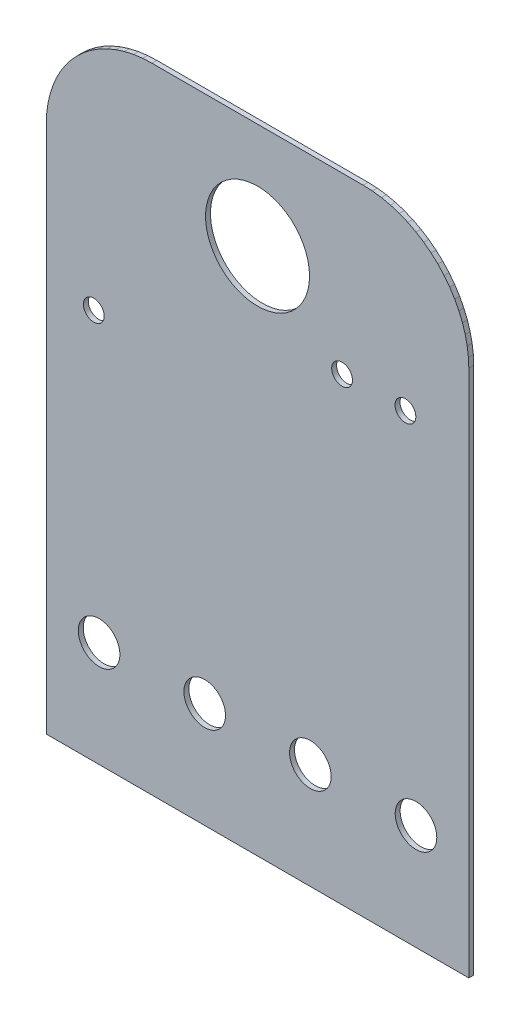
SolidWorks part; units mm, degrees
ref_plane "Front Plane" through (0, 0, 0) normal (0, 0, 1) x (1, 0, 0)
ref_plane "Top Plane" through (0, 0, 0) normal (0, 1, 0) x (1, 0, 0)
ref_plane "Right Plane" through (0, 0, 0) normal (1, 0, 0) x (0, 0, -1)
sketch "Model" plane through (0, 0, 0) normal (0, 0, 1) x (1, 0, 0)
  line L0 (0, 0) -> (258.064, 0)
  line L1 (258.064, 0) -> (258.064, 322.58)
  line L2 (258.064, 322.58) -> (257.8185, 328.2029)
  line L3 (257.8185, 328.2029) -> (257.0839, 333.7831)
  line L4 (257.0839, 333.7831) -> (255.8657, 339.278)
  line L5 (255.8657, 339.278) -> (254.1732, 344.6458)
  line L6 (254.1732, 344.6458) -> (252.0194, 349.8456)
  line L7 (252.0194, 349.8456) -> (249.4205, 354.838)
  line L8 (249.4205, 354.838) -> (246.3964, 359.5849)
  line L9 (246.3964, 359.5849) -> (242.9701, 364.0501)
  line L10 (242.9701, 364.0501) -> (239.1677, 368.1997)
  line L11 (239.1677, 368.1997) -> (235.0181, 372.0021)
  line L12 (235.0181, 372.0021) -> (230.5529, 375.4284)
  line L13 (230.5529, 375.4284) -> (225.806, 378.4525)
  line L14 (225.806, 378.4525) -> (220.8136, 381.0514)
  line L15 (220.8136, 381.0514) -> (215.6138, 383.2052)
  line L16 (215.6138, 383.2052) -> (210.246, 384.8977)
  line L17 (210.246, 384.8977) -> (204.7511, 386.1159)
  line L18 (204.7511, 386.1159) -> (199.1709, 386.8505)
  line L19 (199.1709, 386.8505) -> (193.548, 387.096)
  line L20 (193.548, 387.096) -> (64.516, 387.096)
  line L21 (64.516, 387.096) -> (58.8931, 386.8505)
  line L22 (58.8931, 386.8505) -> (53.3129, 386.1159)
  line L23 (53.3129, 386.1159) -> (47.818, 384.8977)
  line L24 (47.818, 384.8977) -> (42.4502, 383.2052)
  line L25 (42.4502, 383.2052) -> (37.2504, 381.0514)
  line L26 (37.2504, 381.0514) -> (32.258, 378.4525)
  line L27 (32.258, 378.4525) -> (27.5111, 375.4284)
  line L28 (27.5111, 375.4284) -> (23.0459, 372.0021)
  line L29 (23.0459, 372.0021) -> (18.8963, 368.1997)
  line L30 (18.8963, 368.1997) -> (15.0939, 364.0501)
  line L31 (15.0939, 364.0501) -> (11.6676, 359.5849)
  line L32 (11.6676, 359.5849) -> (8.6435, 354.838)
  line L33 (8.6435, 354.838) -> (6.0446, 349.8456)
  line L34 (6.0446, 349.8456) -> (3.8908, 344.6458)
  line L35 (3.8908, 344.6458) -> (2.1983, 339.278)
  line L36 (2.1983, 339.278) -> (0.9801, 333.7831)
  line L37 (0.9801, 333.7831) -> (0.2455, 328.2029)
  line L38 (0.2455, 328.2029) -> (0, 322.58)
  line L39 (0, 322.58) -> (0, 0)
  circle A0 centre (129.032, 322.58) radius 31.75
  circle A1 centre (225.806, 64.516) radius 12.7
  circle A2 centre (161.29, 64.516) radius 12.7
  circle A3 centre (96.774, 64.516) radius 12.7
  circle A4 centre (32.258, 64.516) radius 12.7
  circle A5 centre (29.0322, 238.7092) radius 6.35
  circle A6 centre (219.3544, 280.6446) radius 6.35
  circle A7 centre (180.6448, 280.6446) radius 6.35
extrude "Boss-Extrude1" add sketch "Model" along normal blind 3
